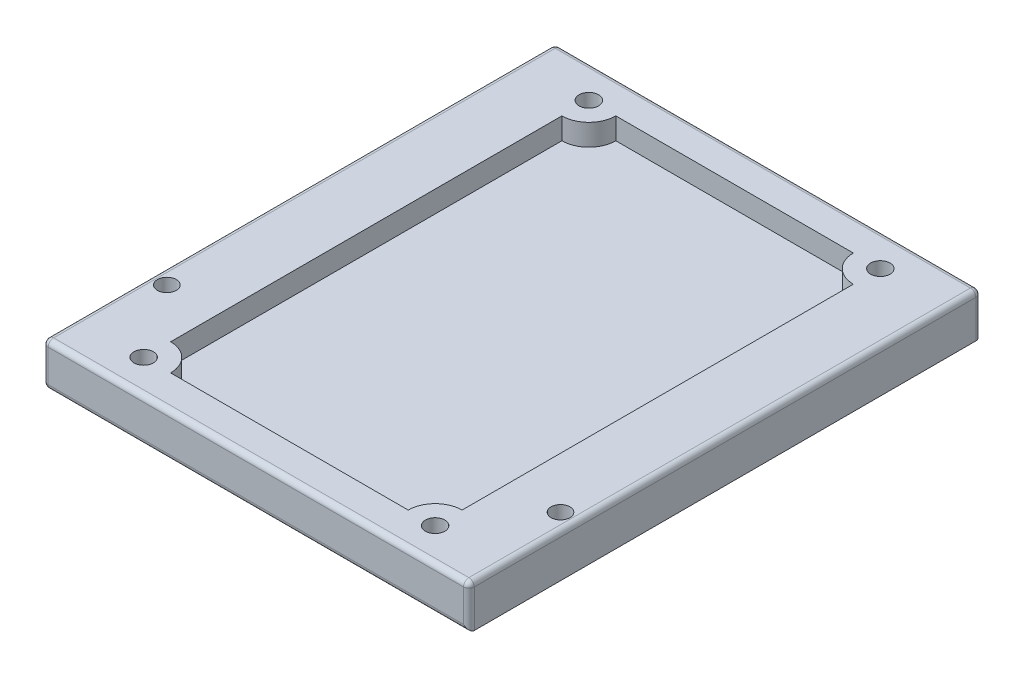
SolidWorks part; units mm, degrees
ref_plane "Front Plane" through (0, 0, 0) normal (0, 0, 1) x (1, 0, 0)
ref_plane "Top Plane" through (0, 0, 0) normal (0, 1, 0) x (1, 0, 0)
ref_plane "Right Plane" through (0, 0, 0) normal (1, 0, 0) x (0, 0, -1)
sketch "Sketch1" plane through (0, 0, 0) normal (0, 1, 0) x (1, 0, 0)
  line L0 (39.5, 95) -> (39.5, 0) construction
  line L1 (0, 0) -> (79, 0)
  line L2 (0, 0) -> (0, 95)
  line L3 (0, 95) -> (79, 95)
  line L4 (79, 0) -> (79, 95)
  circle A0 centre (3, 20) radius 1.75
  circle A1 centre (12.475, 6.225) radius 1.65 construction
  circle A2 centre (12.475, 88.775) radius 1.65 construction
  circle A3 centre (76, 20) radius 1.75
  circle A4 centre (66.525, 6.225) radius 1.65 construction
  circle A5 centre (66.525, 88.775) radius 1.65 construction
  point P20 (39.5, 0)
  dimension "D2" = 3
  dimension "D3" = 3.5
  dimension "D5" = 20
  dimension "D6" = 12.475
  dimension "D7" = 3.3
  dimension "D8" = 12.475
  dimension "D9" = 82.55
  dimension "D10" = 3.3
  dimension "D11" = 6.225
  dimension "D1" = 79
  dimension "D4" = 95
extrude "Boss-Extrude1" add sketch "Sketch1" along normal blind 8
sketch "Sketch3" plane through (0, 0, 0) normal (0, -1, 0) x (1, 0, 0)
  point P0 (12.475, -6.225)
  point P1 (66.525, -6.225)
  point P3 (66.525, -88.775)
  point P5 (12.475, -88.775)
hole_wizard "CBORE for M3 SHCS1" positions "Sketch3" profile "Sketch4" counterbore size "M3" standard "ANSI Metric" end condition through all
sketch "Sketch4" plane through (12.475, 0, -6.225) normal (1, 0, 0) x (0, 0, -1)
  line L0 (0, 0) -> (0, 8)
  line L1 (0, 8) -> (1.8, 8)
  line L3 (1.8, 8) -> (1.8, 3)
  line L4 (1.8, 3) -> (3.25, 3)
  line L5 (3.25, 3) -> (3.25, 0)
  line L7 (3.25, 0) -> (0, 0)
  line L11 (0, -6.35) -> (0, 107.95) construction
  dimension "Thru Hole Dia." = 3.6
  dimension "Thru Hole Depth" = 8
  dimension "C'Bore Dia." = 6.5
  dimension "C'Bore Depth" = 3
sketch "Sketch5" plane through (0, 8, 0) normal (0, 1, 0) x (1, 0, 0)
  line L1 (17.475, 88.775) -> (61.525, 88.775)
  line L2 (12.475, 83.775) -> (12.475, 11.225)
  line L3 (17.475, 6.225) -> (61.525, 6.225)
  line L4 (66.525, 83.775) -> (66.525, 11.225)
  circle A0 centre (12.475, 88.775) radius 1.65 construction
  circle A1 centre (12.475, 6.225) radius 1.65 construction
  arc A3 (12.475, 83.775) -> (17.475, 88.775) centre (12.475, 88.775) ccw
  arc A4 (61.525, 88.775) -> (66.525, 83.775) centre (66.525, 88.775) ccw
  arc A5 (66.525, 11.225) -> (61.525, 6.225) centre (66.525, 6.225) ccw
  arc A6 (17.475, 6.225) -> (12.475, 11.225) centre (12.475, 6.225) ccw
  dimension "D3" = 54.05
  dimension "D1" = 0
  dimension "D2" = 0
extrude "Cut-Extrude1" cut sketch "Sketch5" against normal blind 4
sketch "Sketch6" plane through (0, 0, 0) normal (0, -1, 0) x (1, 0, 0)
  line L1 (9.475, -35) -> (14.475, -35)
  line L2 (9.475, -35) -> (9.475, -55)
  line L3 (9.475, -55) -> (14.475, -55)
  line L4 (14.475, -35) -> (14.475, -55)
  dimension "D1" = 5
  dimension "D2" = 20
  dimension "D3" = 3
  dimension "D4" = 15
extrude "Boss-Extrude2" add sketch "Sketch6" along normal blind 8.8
sketch "Sketch7" plane through (0, 0, -55) normal (0, 0, -1) x (-1, 0, 0)
  line L0 (-14.475, -8.8) -> (-14.475, 0) construction
  line L1 (-9.475, 0) -> (-12.675, 0)
  line L2 (-9.475, 0) -> (-9.475, -6.8)
  line L3 (-9.475, -6.8) -> (-12.675, -6.8)
  line L4 (-12.675, 0) -> (-12.675, -6.8)
  dimension "D1" = 6.8
  dimension "D2" = 1.8
extrude "Cut-Extrude2" cut sketch "Sketch7" against normal through all
fillet "Fillet1" radius 6 1 edges at (14.475, 0, -45) second distance 8 first distance on face at (12.475, 0, -9.475)
fillet "Fillet2" radius 1 10 edges at (0, 4, 0) (39.5, 8, 0) (79, 4, 0) (79, 4, -95) (79, 8, -47.5) (39.5, 8, -95) (0, 4, -95) (0, 8, -47.5) (0, 0, -47.5) (39.5, 0, 0)
